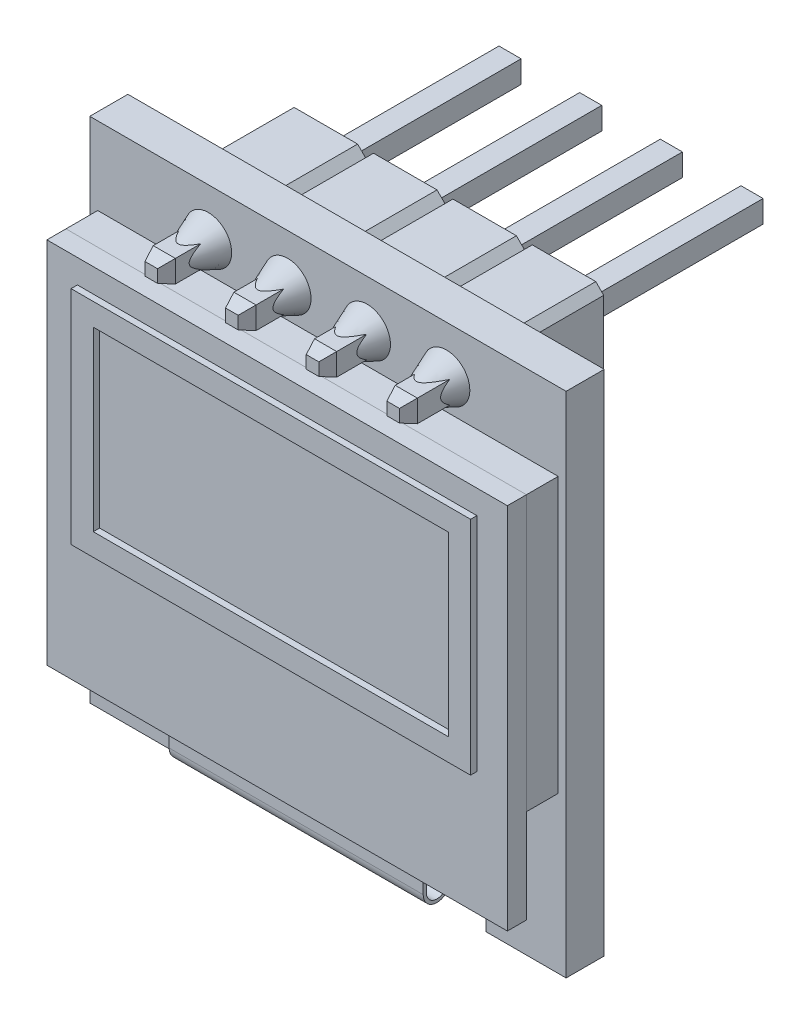
SolidWorks part; units mm, degrees
other "Camera1"
ref_plane "Front Plane" through (0, 0, 0) normal (0, 0, 1) x (1, 0, 0)
ref_plane "Top Plane" through (0, 0, 0) normal (0, 1, 0) x (1, 0, 0)
ref_plane "Right Plane" through (0, 0, 0) normal (1, 0, 0) x (0, 0, -1)
sketch "Sketch1" plane through (0, 0, 0) normal (0, 0, 1) x (1, 0, 0)
  line L0 (159.3832, 442.5757) -> (174.3832, 442.5757) construction
  line L1 (171.815, 426.5556) -> (174.3341, 426.5556)
  line L2 (159.3341, 442.5556) -> (174.3341, 442.5556)
  line L3 (159.3341, 442.5556) -> (159.3341, 426.5556)
  line L4 (159.3341, 426.5556) -> (161.8532, 426.5556)
  line L5 (174.3341, 442.5556) -> (174.3341, 426.5556)
  line L7 (161.8532, 426.5556) -> (161.8532, 427.5104)
  line L8 (161.8532, 427.5104) -> (171.815, 427.5104)
  line L9 (171.815, 426.5556) -> (171.815, 427.5104)
  line L10 (162.72, 441.4156) -> (163.417, 440.7156) construction
  line L11 (160.5441, 439.3613) -> (173.1241, 439.3613)
  line L12 (160.5441, 439.3613) -> (160.5441, 432.3813)
  line L13 (160.5441, 432.3813) -> (173.1241, 432.3813)
  line L14 (173.1241, 439.3613) -> (173.1241, 432.3813)
  line L15 (161.2441, 438.6613) -> (172.4241, 438.6613)
  line L16 (161.2441, 438.6613) -> (161.2441, 433.0813)
  line L17 (161.2441, 433.0813) -> (172.4241, 433.0813)
  line L18 (172.4241, 438.6613) -> (172.4241, 433.0813)
  line L19 (159.5841, 440.111) -> (174.0841, 440.111)
  line L20 (159.5841, 440.111) -> (159.5841, 428.511)
  line L21 (159.5841, 428.511) -> (174.0841, 428.511)
  line L22 (174.0841, 440.111) -> (174.0841, 428.511)
  line L23 (162.72, 441.4156) -> (163.417, 441.4156)
  line L24 (162.72, 441.4156) -> (162.72, 440.7156)
  line L25 (162.72, 440.7156) -> (163.417, 440.7156)
  line L26 (163.417, 441.4156) -> (163.417, 440.7156)
  line L27 (163.417, 441.4156) -> (162.72, 440.7156) construction
  line L28 (165.26, 441.4156) -> (165.957, 441.4156)
  line L29 (165.26, 441.4156) -> (165.26, 440.7156)
  line L30 (165.26, 440.7156) -> (165.957, 440.7156)
  line L31 (165.957, 441.4156) -> (165.957, 440.7156)
  line L32 (167.8, 441.4156) -> (168.497, 441.4156)
  line L33 (167.8, 441.4156) -> (167.8, 440.7156)
  line L34 (167.8, 440.7156) -> (168.497, 440.7156)
  line L35 (168.497, 441.4156) -> (168.497, 440.7156)
  line L36 (170.34, 441.4156) -> (171.037, 441.4156)
  line L37 (170.34, 441.4156) -> (170.34, 440.7156)
  line L38 (170.34, 440.7156) -> (171.037, 440.7156)
  line L39 (171.037, 441.4156) -> (171.037, 440.7156)
  line L40 (161.2441, 435.8713) -> (160.5441, 435.8713) construction
  line L41 (160.5441, 435.8713) -> (159.5841, 435.8713) construction
  line L42 (159.5841, 435.8713) -> (159.3341, 435.8713) construction
  line L43 (172.4241, 435.8713) -> (173.1241, 435.8713) construction
  line L44 (173.1241, 435.8713) -> (174.0841, 435.8713) construction
  line L45 (174.0841, 435.8713) -> (174.3341, 435.8713) construction
  line L46 (166.8341, 427.5104) -> (166.8341, 442.5556) construction
  dimension "D1" = 15
  dimension "D2" = 16
  dimension "D3" = 0.6969
  dimension "D4" = 0.7
  dimension "D5" = 15
  dimension "D6" = 14.5
  dimension "D7" = 12.58
  dimension "D8" = 11.18
  dimension "D9" = 11.6
  dimension "D10" = 6.98
  dimension "D11" = 5.58
  dimension "D12" = 4
extrude "Boss-Extrude1" add sketch "Sketch1" against normal blind 1.2 contours L9 L1 L5 L2 L3 L4 L7 L8 L19 L22 L21 L20 L23 L26 L25 L24 L28 L31 L30 L29 L32 L35 L34 L33 L36 L39 L38 L37 | L22 L19 L20 L21 L11 L14 L13 L12 | L14 L11 L12 L13 L15 L18 L17 L16 | L18 L15 L16 L17 region at (172.0343, 427.033, 0) region at (166.8341, 439.2174, 0) region at (166.8341, 435.8713, 0) region at (166.8341, 439.9253, 0)
extrude "Boss-Extrude2" add sketch "Sketch1<3>" along normal blind 1.8 and the other way blind 9.7 contours L26 L23 L24 L25 | L31 L28 L29 L30 | L35 L32 L33 L34 | L39 L36 L37 L38 region at (163.0685, 441.0656, 0) region at (165.6085, 441.0656, 0) region at (168.1485, 441.0656, 0) region at (170.6885, 441.0656, 0)
sketch "Sketch1<3>" plane through (0, 0, 0) normal (0, 0, 1) x (1, 0, 0) same geometry as "Sketch1"
extrude "Boss-Extrude3" add sketch "Sketch1<4>" against normal blind 0.6 from offset 1.6 contours L22 L19 L20 L21 L11 L14 L13 L12 region at (166.8341, 439.9253, 0)
sketch "Sketch1<4>" plane through (0, 0, 0) normal (0, 0, 1) x (1, 0, 0) same geometry as "Sketch1"
extrude "Boss-Extrude4" add sketch "Sketch1<5>" along normal blind 1.8 contours L14 L11 L12 L13 L15 L18 L17 L16 region at (166.8341, 439.2174, 0)
sketch "Sketch1<5>" plane through (0, 0, 0) normal (0, 0, 1) x (1, 0, 0) same geometry as "Sketch1"
extrude "Boss-Extrude5" add sketch "Sketch1<6>" along normal blind 1.6 contours L18 L15 L16 L17 region at (166.8341, 435.8713, 0)
sketch "Sketch1<6>" plane through (0, 0, 0) normal (0, 0, 1) x (1, 0, 0) same geometry as "Sketch1"
sketch "Sketch2" plane through (0, 0, -1.2) normal (0, 0, -1) x (-1, 0, 0)
  line L0 (-162.72, 441.4156) -> (-163.417, 440.7156) construction
  line L1 (-164.0685, 442.3156) -> (-162.0685, 442.3156)
  line L2 (-164.3185, 442.0656) -> (-164.3185, 440.0656)
  line L3 (-164.0685, 439.8156) -> (-162.0685, 439.8156)
  line L4 (-161.8185, 442.0656) -> (-161.8185, 440.0656)
  line L5 (-164.3185, 442.3156) -> (-161.8185, 439.8156) construction
  line L6 (-164.3185, 439.8156) -> (-161.8185, 442.3156) construction
  line L7 (-164.3185, 442.0656) -> (-164.0685, 442.3156)
  line L8 (-164.3185, 440.0656) -> (-164.0685, 439.8156)
  line L9 (-162.0685, 439.8156) -> (-161.8185, 440.0656)
  line L10 (-162.0685, 442.3156) -> (-161.8185, 442.0656)
  point P0 (-163.0685, 441.0656)
  dimension "D1" = 2.5
  dimension "D2" = 2.5
extrude "Boss-Extrude6" add sketch "Sketch2" along normal blind 2.5 separate body
pattern_linear "LPattern1" count 4 spacing 2.5 along (1, 0, 0) of "Boss-Extrude6"
sketch "Sketch3" plane through (0, 0, 1.6) normal (0, 0, 1) x (1, 0, 0)
  line L0 (174.0841, 440.111) -> (174.0841, 428.511) construction
  line L1 (159.5841, 440.111) -> (174.0841, 440.111)
  line L2 (159.5841, 440.111) -> (159.5841, 431.4651)
  line L3 (159.5841, 431.4651) -> (174.0841, 431.4651)
  line L4 (174.0841, 440.111) -> (174.0841, 431.4651)
extrude "Boss-Extrude7" add sketch "Sketch3" against normal up to surface (1.6 mm away) from offset 0.6 separate body up to face at (166.8341, 435.8713, 0) offset against normal yes
sketch "Sketch4" plane through (0, 0, 0) normal (0, 0, 1) x (1, 0, 0)
  circle A0 centre (163.0685, 441.0656) radius 0.7336
extrude "Boss-Extrude8" add sketch "Sketch4" along normal blind 1 draft 22 separate body
pattern_linear "LPattern2" count 4 spacing 2.5 along (1, 0, 0) of "Boss-Extrude8"
ref_plane "Plane1" through (166.8341, 0, 0) normal (-1, 0, 0) x (0, 0, 1)
sketch "Sketch6" plane through (166.8341, 0, 0) normal (-1, 0, 0) x (0, 0, 1)
  line L0 (1, 434.311) -> (1, 427.5776)
  line L1 (1, 440.111) -> (1, 428.511) construction
  line L2 (0.1371, 427.5776) -> (0.1371, 429.9881)
  arc A0 (1, 427.5776) -> (0.1371, 427.5776) centre (0.5686, 427.5776) cw
  point P6 (0.5686, 427.5776)
extrude "Extrude-Thin1" add sketch "Sketch6" along normal mid plane 8 thin thin type one direction wall 0.1
combine bodies "Combine2" operation type add bodies to combine 105 114 113 112 111
combine bodies "Combine3" operation type add bodies to combine 106 107 108 109
chamfer "Chamfer1" distance 0.15 angle 70 4 edges at (170.6885, 440.7156, 1.8) (170.34, 441.0656, 1.8) (170.6885, 441.4156, 1.8) (171.037, 441.0656, 1.8) first distance on face at (170.6885, 441.0656, 1.8)
chamfer "Chamfer2" distance 0.15 angle 70 12 edges at (165.6085, 440.7156, 1.8) (165.26, 441.0656, 1.8) (165.6085, 441.4156, 1.8) (165.957, 441.0656, 1.8) (163.0685, 440.7156, 1.8) (162.72, 441.0656, 1.8) (163.0685, 441.4156, 1.8) (163.417, 441.0656, 1.8) (168.1485, 440.7156, 1.8) (167.8, 441.0656, 1.8) (168.1485, 441.4156, 1.8) (168.497, 441.0656, 1.8) first distance on face at (165.6085, 441.0656, 1.8) first distance on face at (163.0685, 441.0656, 1.8) first distance on face at (168.1485, 441.0656, 1.8)
chamfer "Chamfer3" distance 0.2 angle 45 16 edges at (163.0685, 441.4156, -9.7) (162.72, 441.0656, -9.7) (163.0685, 440.7156, -9.7) (163.417, 441.0656, -9.7) (165.6085, 441.4156, -9.7) (165.26, 441.0656, -9.7) (165.6085, 440.7156, -9.7) (165.957, 441.0656, -9.7) (168.1485, 441.4156, -9.7) (167.8, 441.0656, -9.7) (168.1485, 440.7156, -9.7) (168.497, 441.0656, -9.7) (170.6885, 441.4156, -9.7) (170.34, 441.0656, -9.7) (170.6885, 440.7156, -9.7) (171.037, 441.0656, -9.7)
